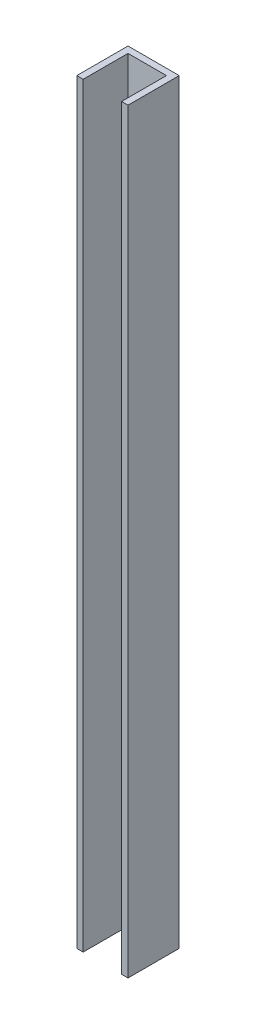
SolidWorks part; units mm, degrees
material "Plain Carbon Steel"
ref_plane "Front Plane" through (0, 0, 0) normal (0, 0, 1) x (1, 0, 0)
ref_plane "Top Plane" through (0, 0, 0) normal (0, 1, 0) x (1, 0, 0)
ref_plane "Right Plane" through (0, 0, 0) normal (1, 0, 0) x (0, 0, -1)
sketch "Sketch1" plane through (0, 0, 0) normal (0, 1, 0) x (1, 0, 0)
  line L0 (0, 0) -> (3.175, 0)
  line L1 (0, 0) -> (0, 25.4)
  line L2 (0, 25.4) -> (25.4, 25.4)
  line L3 (25.4, 25.4) -> (25.4, 0)
  line L4 (25.4, 0) -> (22.225, 0)
  line L5 (22.225, 0) -> (22.225, 22.225)
  line L6 (22.225, 22.225) -> (3.175, 22.225)
  line L7 (3.175, 22.225) -> (3.175, 0)
extrude "Boss-Extrude1" add sketch "Sketch1" along normal blind 374.65 contours L2 L3 L4 L5 L6 L7 L0 L1
